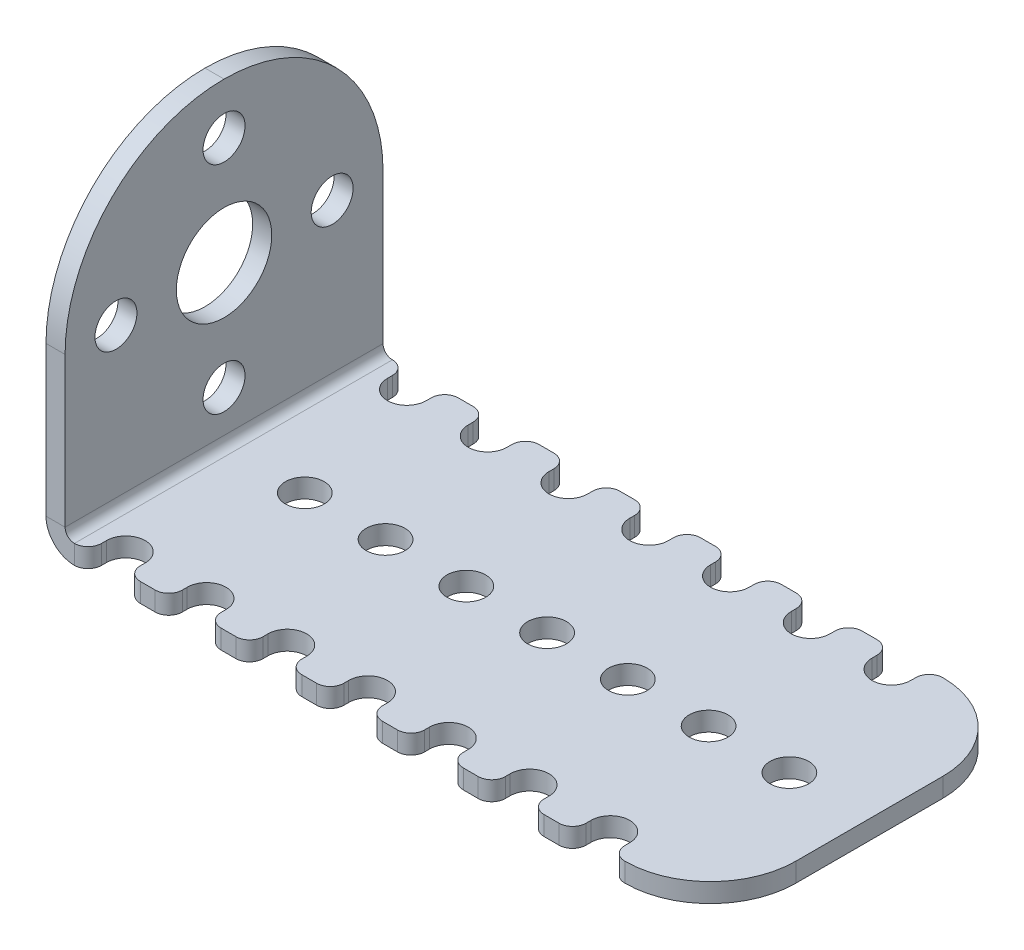
SolidWorks part; units mm, degrees
note: The reader was unsure of these and kept them because the rebuilt part matched: flange length of "Edge-Flange1".
ref_plane "Front Plane" through (0, 0, 0) normal (0, 0, 1) x (1, 0, 0)
ref_plane "Top Plane" through (0, 0, 0) normal (0, 1, 0) x (1, 0, 0)
ref_plane "Right Plane" through (0, 0, 0) normal (1, 0, 0) x (0, 0, -1)
sketch "Sketch1" plane through (0, 0, 0) normal (0, 1, 0) x (1, 0, 0)
  line L1 (-25, 12.5) -> (25, 12.5)
  line L2 (-25, 12.5) -> (-25, -12.5)
  line L3 (-25, -12.5) -> (25, -12.5)
  line L4 (25, 12.5) -> (25, -12.5)
  point P4 (25, 0)
  point P6 (0, 12.5)
  dimension "D1" = 50
  dimension "D2" = 25
base flange "Base-Flange1" sketch "Sketch1" thickness 1.5 reverse thickness direction no parameters "D1"=0.7366
edge flange "Edge-Flange1" sketch "Sketch8" flange angle 90 flange length 25 flange position bend outside bend radius 0.7366 thickness 1.5 relief rectangular parameters "D6"=10
sketch "Sketch8" plane through (-25, 0, 0) normal (-1, 0, 0) x (0, 0, 1)
  line L2 (-12.5, 0) -> (-12.5, 25)
  line L3 (-12.5, 25) -> (12.5, 25)
  line L4 (12.5, 25) -> (12.5, 0)
  line L5 (-12.5, 0) -> (12.5, 0) construction
  line L6 (-12.5, 0) -> (12.5, 0)
bend "EdgeBend1" bend radius 0.7366 bend angle 90 parameters "D5"=1
fillet "Fillet1" radius 12.5 2 edges at (-26.4866, 25, -12.5) (-26.4866, 25, 12.5)
sketch "Sketch11" plane through (-27.2366, 0, 0) normal (-1, 0, 0) x (0, 0, 1)
  line L0 (-12.5, -1.5) -> (12.5, -1.5) construction
  circle A0 centre (0, 12.5) radius 3.75
  arc A1 (12.5, 12.5) -> (0, 25) centre (0, 12.5) ccw construction
  circle A2 centre (0, 21) radius 1.65
  circle A3 centre (8.5, 12.5) radius 1.65
  circle A4 centre (0, 4) radius 1.65
  circle A5 centre (-8.5, 12.5) radius 1.65
  point P18 (0, 12.5)
  dimension "D2" = 7.5
  dimension "D3" = 3.3
  dimension "D1" = 14
  dimension "D4" = 8.5
  dimension "D5" = 4
extrude "Cut-Extrude1" cut sketch "Sketch11" against normal up to next normal cut yes
sketch "Sketch14" plane through (0, 0, 0) normal (0, 1, 0) x (1, 0, 0)
  line L0 (-25.7366, 12.5) -> (-25.7366, -12.5) construction
  line L1 (-10.5536, 9.525) -> (-1.8477, 9.525) construction
  line L2 (2.8269, -9.525) -> (11.5631, -9.525) construction
  line L3 (-27.2366, 12.5) -> (-27.2366, 0) construction
  line L4 (-20.8866, 11.049) -> (-20.8866, 11.4346)
  line L5 (25, 12.5) -> (-25, 12.5) construction
  line L6 (-23.9346, 11.049) -> (-23.9346, 11.4346)
  line L7 (-25, 12.5) -> (-25, -12.5) construction
  line L8 (-22.4106, 11.049) -> (-22.4106, 10.139) construction
  line L9 (-17.5846, 11.049) -> (-17.5846, 11.4346)
  line L10 (-14.5366, 11.049) -> (-14.5366, 11.4346)
  line L11 (-11.2346, 11.049) -> (-11.2346, 11.4346)
  line L12 (-8.1866, 11.049) -> (-8.1866, 11.4346)
  line L13 (-4.8846, 11.049) -> (-4.8846, 11.4346)
  line L14 (-1.8366, 11.049) -> (-1.8366, 11.4346)
  line L15 (1.4654, 11.049) -> (1.4654, 11.4346)
  line L16 (4.5134, 11.049) -> (4.5134, 11.4346)
  line L17 (7.8154, 11.049) -> (7.8154, 11.4346)
  line L18 (10.8634, 11.049) -> (10.8634, 11.4346)
  line L19 (14.1654, 11.049) -> (14.1654, 11.4346)
  line L20 (17.2134, 11.049) -> (17.2134, 11.4346)
  line L21 (-23.9346, 11.4346) -> (-17.5846, 11.4346) construction
  line L22 (-19.8212, 12.5) -> (-18.65, 12.5)
  line L23 (-13.4712, 12.5) -> (-12.3, 12.5)
  line L24 (-7.1212, 12.5) -> (-5.95, 12.5)
  line L25 (-0.7712, 12.5) -> (0.4, 12.5)
  line L26 (5.5788, 12.5) -> (6.75, 12.5)
  line L27 (11.9288, 12.5) -> (13.1, 12.5)
  line L28 (42.26, 0) -> (56.1088, 0) construction
  line L29 (18.2788, 14.3043) -> (-25, 14.3043)
  line L30 (-25, 14.3043) -> (-25, 12.5)
  line L31 (25, -12.5) -> (25, 12.5) construction
  line L32 (-23.9346, -11.4346) -> (-17.5846, -11.4346) construction
  line L33 (25, 5.7788) -> (25, 3.0862)
  line L34 (25, 3.0862) -> (30.0909, 3.0862)
  line L35 (30.0909, 3.0862) -> (30.0909, 14.3043)
  line L36 (30.0909, 14.3043) -> (18.2788, 14.3043)
  line L37 (-22.4106, -11.049) -> (-22.4106, -10.139) construction
  line L38 (30.0909, -14.3043) -> (18.2788, -14.3043)
  line L39 (30.0909, -3.0862) -> (30.0909, -14.3043)
  line L40 (25, -3.0862) -> (30.0909, -3.0862)
  line L41 (25, -5.7788) -> (25, -3.0862)
  line L42 (-25, -14.3043) -> (-25, -12.5)
  line L43 (18.2788, -14.3043) -> (-25, -14.3043)
  line L44 (11.9288, -12.5) -> (13.1, -12.5)
  line L45 (5.5788, -12.5) -> (6.75, -12.5)
  line L46 (-0.7712, -12.5) -> (0.4, -12.5)
  line L47 (-7.1212, -12.5) -> (-5.95, -12.5)
  line L48 (-13.4712, -12.5) -> (-12.3, -12.5)
  line L49 (-19.8212, -12.5) -> (-18.65, -12.5)
  line L50 (17.2134, -11.049) -> (17.2134, -11.4346)
  line L51 (14.1654, -11.049) -> (14.1654, -11.4346)
  line L52 (10.8634, -11.049) -> (10.8634, -11.4346)
  line L53 (7.8154, -11.049) -> (7.8154, -11.4346)
  line L54 (4.5134, -11.049) -> (4.5134, -11.4346)
  line L55 (1.4654, -11.049) -> (1.4654, -11.4346)
  line L56 (-1.8366, -11.049) -> (-1.8366, -11.4346)
  line L57 (-4.8846, -11.049) -> (-4.8846, -11.4346)
  line L58 (-8.1866, -11.049) -> (-8.1866, -11.4346)
  line L59 (-11.2346, -11.049) -> (-11.2346, -11.4346)
  line L60 (-14.5366, -11.049) -> (-14.5366, -11.4346)
  line L61 (-17.5846, -11.049) -> (-17.5846, -11.4346)
  line L62 (-23.9346, -11.049) -> (-23.9346, -11.4346)
  line L63 (-20.8866, -11.049) -> (-20.8866, -11.4346)
  circle A0 centre (-19.3866, 0) radius 1.524
  circle A1 centre (-13.0366, 0) radius 1.524
  circle A2 centre (-6.6866, 0) radius 1.524
  circle A3 centre (-0.3366, 0) radius 1.524
  circle A4 centre (6.0134, 0) radius 1.524
  circle A5 centre (12.3634, 0) radius 1.524
  circle A6 centre (18.7134, 0) radius 1.524
  arc A7 (-23.9346, 11.049) -> (-20.8866, 11.049) centre (-22.4106, 11.049) ccw
  arc A8 (-23.9346, 11.4346) -> (-25, 12.5) centre (-25, 11.4346) ccw
  arc A9 (-20.8866, 11.4346) -> (-19.8212, 12.5) centre (-19.8212, 11.4346) cw
  arc A10 (-17.5846, 11.4346) -> (-18.65, 12.5) centre (-18.65, 11.4346) ccw
  arc A11 (-17.5846, 11.049) -> (-14.5366, 11.049) centre (-16.0606, 11.049) ccw
  arc A12 (-14.5366, 11.4346) -> (-13.4712, 12.5) centre (-13.4712, 11.4346) cw
  arc A13 (-11.2346, 11.4346) -> (-12.3, 12.5) centre (-12.3, 11.4346) ccw
  arc A14 (-11.2346, 11.049) -> (-8.1866, 11.049) centre (-9.7106, 11.049) ccw
  arc A15 (-8.1866, 11.4346) -> (-7.1212, 12.5) centre (-7.1212, 11.4346) cw
  arc A16 (-4.8846, 11.4346) -> (-5.95, 12.5) centre (-5.95, 11.4346) ccw
  arc A17 (-4.8846, 11.049) -> (-1.8366, 11.049) centre (-3.3606, 11.049) ccw
  arc A18 (-1.8366, 11.4346) -> (-0.7712, 12.5) centre (-0.7712, 11.4346) cw
  arc A19 (1.4654, 11.4346) -> (0.4, 12.5) centre (0.4, 11.4346) ccw
  arc A20 (1.4654, 11.049) -> (4.5134, 11.049) centre (2.9894, 11.049) ccw
  arc A21 (4.5134, 11.4346) -> (5.5788, 12.5) centre (5.5788, 11.4346) cw
  arc A22 (7.8154, 11.4346) -> (6.75, 12.5) centre (6.75, 11.4346) ccw
  arc A23 (7.8154, 11.049) -> (10.8634, 11.049) centre (9.3394, 11.049) ccw
  arc A24 (10.8634, 11.4346) -> (11.9288, 12.5) centre (11.9288, 11.4346) cw
  arc A25 (14.1654, 11.4346) -> (13.1, 12.5) centre (13.1, 11.4346) ccw
  arc A26 (14.1654, 11.049) -> (17.2134, 11.049) centre (15.6894, 11.049) ccw
  arc A27 (17.2134, 11.4346) -> (18.2788, 12.5) centre (18.2788, 11.4346) cw
  arc A28 (18.2788, 12.5) -> (25, 5.7788) centre (18.2788, 5.7788) cw
  arc A29 (18.2788, -12.5) -> (25, -5.7788) centre (18.2788, -5.7788) ccw
  arc A30 (17.2134, -11.4346) -> (18.2788, -12.5) centre (18.2788, -11.4346) ccw
  arc A31 (14.1654, -11.049) -> (17.2134, -11.049) centre (15.6894, -11.049) cw
  arc A32 (14.1654, -11.4346) -> (13.1, -12.5) centre (13.1, -11.4346) cw
  arc A33 (10.8634, -11.4346) -> (11.9288, -12.5) centre (11.9288, -11.4346) ccw
  arc A34 (7.8154, -11.049) -> (10.8634, -11.049) centre (9.3394, -11.049) cw
  arc A35 (7.8154, -11.4346) -> (6.75, -12.5) centre (6.75, -11.4346) cw
  arc A36 (4.5134, -11.4346) -> (5.5788, -12.5) centre (5.5788, -11.4346) ccw
  arc A37 (1.4654, -11.049) -> (4.5134, -11.049) centre (2.9894, -11.049) cw
  arc A38 (1.4654, -11.4346) -> (0.4, -12.5) centre (0.4, -11.4346) cw
  arc A39 (-1.8366, -11.4346) -> (-0.7712, -12.5) centre (-0.7712, -11.4346) ccw
  arc A40 (-4.8846, -11.049) -> (-1.8366, -11.049) centre (-3.3606, -11.049) cw
  arc A41 (-4.8846, -11.4346) -> (-5.95, -12.5) centre (-5.95, -11.4346) cw
  arc A42 (-8.1866, -11.4346) -> (-7.1212, -12.5) centre (-7.1212, -11.4346) ccw
  arc A43 (-11.2346, -11.049) -> (-8.1866, -11.049) centre (-9.7106, -11.049) cw
  arc A44 (-11.2346, -11.4346) -> (-12.3, -12.5) centre (-12.3, -11.4346) cw
  arc A45 (-14.5366, -11.4346) -> (-13.4712, -12.5) centre (-13.4712, -11.4346) ccw
  arc A46 (-17.5846, -11.049) -> (-14.5366, -11.049) centre (-16.0606, -11.049) cw
  arc A47 (-17.5846, -11.4346) -> (-18.65, -12.5) centre (-18.65, -11.4346) cw
  arc A48 (-20.8866, -11.4346) -> (-19.8212, -12.5) centre (-19.8212, -11.4346) ccw
  arc A49 (-23.9346, -11.4346) -> (-25, -12.5) centre (-25, -11.4346) cw
  arc A50 (-23.9346, -11.049) -> (-20.8866, -11.049) centre (-22.4106, -11.049) cw
  dimension "D1" = 3.048
  dimension "D2" = 6.35
  dimension "D4" = 6.35
  dimension "D5" = 19.05
  dimension "D6" = 9.525
  dimension "D7" = 4.826
  dimension "D9" = 6.35
  dimension "D3" = 7
  dimension "D8" = 7
extrude "Cut-Extrude2" cut sketch "Sketch14" against normal up to next
sketch "Sketch17" plane through (0, 0, 0) normal (0, 1, 0) x (1, 0, 0)
  circle A0 centre (-9.7106, 11.049) radius 1.5
  circle A1 centre (2.9894, 11.049) radius 1.5
  circle A2 centre (15.6894, 11.049) radius 1.5
  circle A3 centre (15.6894, -11.049) radius 1.5
  circle A4 centre (2.9894, -11.049) radius 1.5
  circle A5 centre (-9.7106, -11.049) radius 1.5
  arc A7 (1.4654, 11.049) -> (4.5134, 11.049) centre (2.9894, 11.049) ccw construction
  arc A8 (-11.2346, 11.049) -> (-8.1866, 11.049) centre (-9.7106, 11.049) ccw construction
  arc A9 (14.1654, 11.049) -> (17.2134, 11.049) centre (15.6894, 11.049) ccw construction
  arc A10 (-8.1866, -11.049) -> (-11.2346, -11.049) centre (-9.7106, -11.049) ccw construction
  arc A11 (4.5134, -11.049) -> (1.4654, -11.049) centre (2.9894, -11.049) ccw construction
  arc A12 (17.2134, -11.049) -> (14.1654, -11.049) centre (15.6894, -11.049) ccw construction
  dimension "D1" = 3
sketch "Bend-Lines1" plane through (0, 0, 0) normal (0, 1, 0) x (1, 0, 0)
sketch "Bounding-Box1" plane through (0, 0, 0) normal (0, 1, 0) x (1, 0, 0)
sheet metal parameters "Sheet-Metal(1)" thickness 1.5 parameters "D1"=0.7366
flat pattern "Flat-Pattern(1)" [suppressed]
sketch "Bend-Lines2" plane through (0, 0, 0) normal (0, 1, 0) x (1, 0, 0)
sketch "Bounding-Box2" [suppressed] plane through (0, 0, 0) normal (0, 1, 0) x (1, 0, 0)
sheet metal parameters "Sheet-Metal(2)" thickness 1.5 parameters "D1"=0.7366
flat pattern "Flat-Pattern(1)" [suppressed]
sketch "Bend-Lines3" plane through (0, 0, 0) normal (0, 1, 0) x (1, 0, 0)
sketch "Bounding-Box3" [suppressed] plane through (0, 0, 0) normal (0, 1, 0) x (1, 0, 0)
bend of the flat pattern "Flatten-<EdgeBend1>1"
sheet metal parameters "Sheet-Metal(3)" thickness 1.5 parameters "D1"=0.7366
flat pattern "Flat-Pattern(1)" [suppressed]
sketch "Bend-Lines4" plane through (0, 0, 0) normal (0, 1, 0) x (1, 0, 0)
sketch "Bounding-Box4" [suppressed] plane through (0, 0, 0) normal (0, 1, 0) x (1, 0, 0)
bend of the flat pattern "Flatten-<EdgeBend1>2"
sheet metal parameters "Sheet-Metal(4)" thickness 1.5 parameters "D1"=0.7366
flat pattern "Flat-Pattern(1)" [suppressed]
sketch "Bend-Lines5" plane through (0, 0, 0) normal (0, 1, 0) x (1, 0, 0)
sketch "Bounding-Box5" [suppressed] plane through (0, 0, 0) normal (0, 1, 0) x (1, 0, 0)
bend of the flat pattern "Flatten-<EdgeBend1>3"
equation "\"D6@Sketch14\"=\"D5@Sketch14\"/2"
